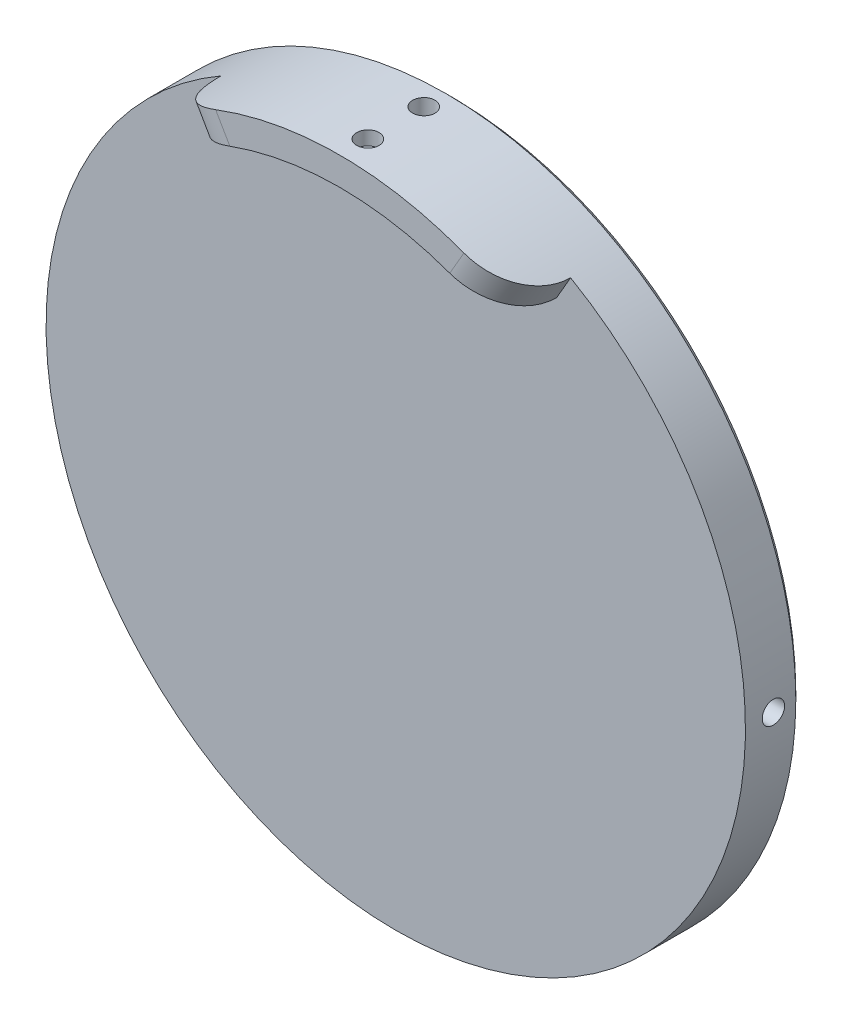
SolidWorks part; units mm, degrees
material "6063-T6"
ref_plane "Ön Düzlem" through (0, 0, 0) normal (0, 0, 1) x (1, 0, 0)
ref_plane "Üst Düzlem" through (0, 0, 0) normal (0, 1, 0) x (1, 0, 0)
ref_plane "Sağ Düzlem" through (0, 0, 0) normal (1, 0, 0) x (0, 0, -1)
sketch "Sketch1" plane through (0, 0, 0) normal (0, 0, 1) x (1, 0, 0)
  circle A0 centre (0, 0) radius 62.5
  dimension "D1" = 125
extrude "Boss-Extrude1" add sketch "Sketch1" along normal mid plane 10 contours A0
sketch "Sketch2" plane through (0, 0, 0) normal (0, 1, 0) x (1, 0, 0)
  circle A0 centre (0, 0) radius 2
  dimension "D1" = 4
extrude "Cut-Extrude1" cut sketch "Sketch2" along normal blind 10 from offset 55
extrude "Cut-Extrude2" cut sketch "Sketch2<2>" against normal blind 10 from offset 55 offset against normal yes
sketch "Sketch2<2>" plane through (0, 0, 0) normal (0, 1, 0) x (1, 0, 0) same geometry as "Sketch2"
sketch "Sketch3" plane through (0, 0, 0) normal (1, 0, 0) x (0, 0, -1)
  circle A0 centre (0, 0) radius 2
  dimension "D1" = 4
extrude "Cut-Extrude3" cut sketch "Sketch3" along normal blind 10 from offset 55
extrude "Cut-Extrude4" cut sketch "Sketch3<2>" against normal blind 10 from offset 55 offset against normal yes
sketch "Sketch3<2>" plane through (0, 0, 0) normal (1, 0, 0) x (0, 0, -1) same geometry as "Sketch3"
sketch "Sketch4" plane through (0, 0, 5) normal (0, 0, 1) x (1, 0, 0)
  line L0 (0, 0) -> (0, 62.5) construction
  line L1 (0, 0) -> (-31.25, 54.1266) construction
  line L2 (0, 0) -> (31.25, 54.1266) construction
  line L3 (-31.25, 54.1266) -> (-28.75, 49.7965)
  line L4 (31.25, 54.1266) -> (28.75, 49.7965)
  arc A0 (31.25, 54.1266) -> (-31.25, 54.1266) centre (0, 0) ccw
  arc A1 (28.75, 49.7965) -> (-28.75, 49.7965) centre (0, 0) ccw
  circle A2 centre (0, 0) radius 62.5 construction
  circle A3 centre (0, 0) radius 62.5 construction
  circle A4 centre (0, 0) radius 57.5 construction
  dimension "D1" = 5
  dimension "D3" = 30
  dimension "D4" = 60
extrude "Boss-Extrude2" add sketch "Sketch4" along normal blind 10
fillet "Fillet1" radius 10 2 edges at (-30, 51.9615, 15) (30, 51.9615, 15)
sketch "Sketch6" plane through (0, 0, 0) normal (0, 1, 0) x (1, 0, 0)
  line L0 (-31.25, -5) -> (31.25, -5) construction
  line L1 (0, -5) -> (0, -10) construction
  circle A0 centre (0, -10) radius 2
  dimension "D2" = 4
  dimension "D1" = 5
extrude "Cut-Extrude5" cut sketch "Sketch6" along normal blind 10 from offset 60
chamfer "Chamfer1" distance 1 angle 45 1 edges at (62.5, 0, -5)
